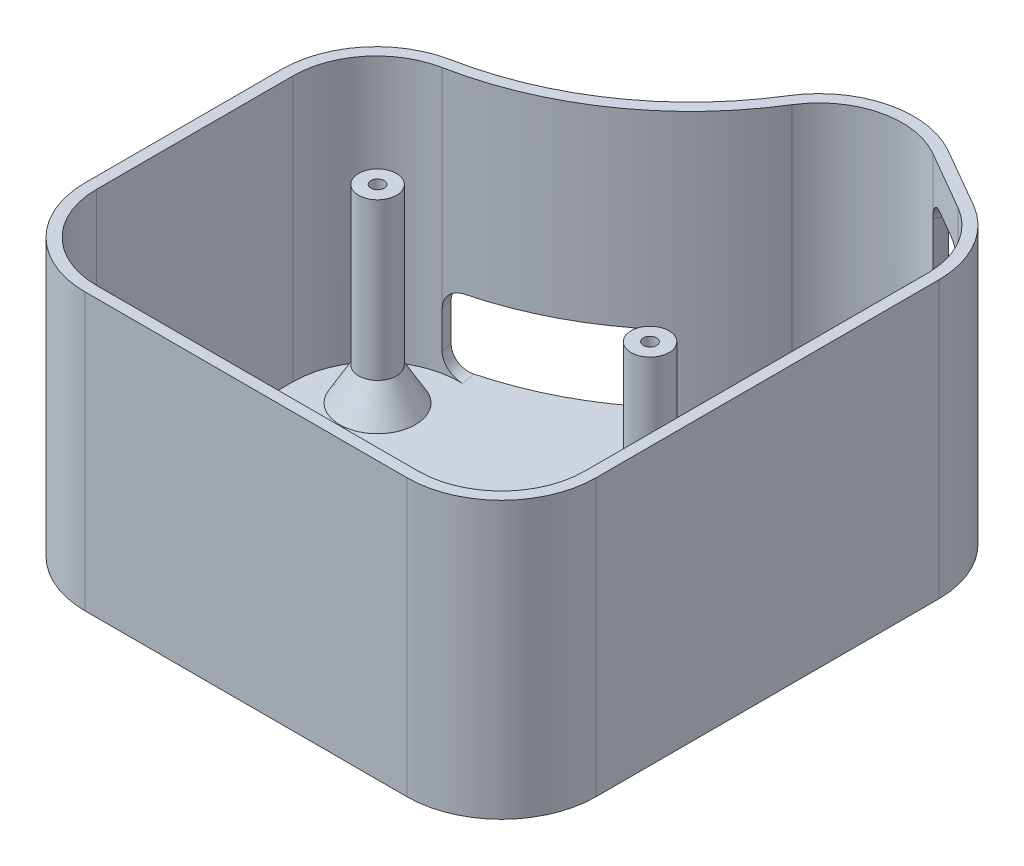
SolidWorks part; units mm, degrees
ref_plane "Front Plane" through (0, 0, 0) normal (0, 0, 1) x (1, 0, 0)
ref_plane "Top Plane" through (0, 0, 0) normal (0, 1, 0) x (1, 0, 0)
ref_plane "Right Plane" through (0, 0, 0) normal (1, 0, 0) x (0, 0, -1)
sketch "Sketch1" plane through (0, 0, 0) normal (0, 1, 0) x (1, 0, 0)
  line L1 (-130, 50) -> (130, 50)
  line L2 (-130, 50) -> (-130, -50)
  line L3 (-130, -50) -> (130, -50)
  line L4 (130, 50) -> (130, -50)
  line L5 (-130, 50) -> (130, -50) construction
  line L6 (-130, -50) -> (130, 50) construction
  point P0 (0, 0)
  dimension "D1" = 260
  dimension "D2" = 100
extrude "Boss-Extrude1" add sketch "Sketch1" along normal blind 3 contours L4 L3 L2 L1
sketch "Sketch4" plane through (0, 3, 0) normal (0, 1, 0) x (1, 0, 0)
  line L0 (-130, 50) -> (130, 50) construction
  line L1 (-77.5342, 30.2911) -> (-130, 0)
  line L2 (-130, 50) -> (-130, -50) construction
  line L3 (77.5342, 30.2911) -> (130, 0)
  line L4 (130, 50) -> (130, -50) construction
  line L5 (0, 0) -> (0, 50) construction
  line L6 (-130, -50) -> (130, -50) construction
  line L7 (-130, 0) -> (-130, 50)
  line L8 (-130, 50) -> (130, 50)
  line L9 (130, 50) -> (130, 0)
  arc A0 (-77.5342, 30.2911) -> (77.5342, 30.2911) centre (0, 50) ccw
  dimension "D1" = 160
  dimension "D2" = 60
  dimension "D3" = 60
  dimension "D4" = 50
extrude "Cut-Extrude1" cut sketch "Sketch4" against normal blind 5
sketch "Sketch5" plane through (0, 3, 0) normal (0, 1, 0) x (1, 0, 0)
  line L0 (-130, -50) -> (130, -50)
  line L1 (130, -50) -> (130, -130)
  line L2 (130, -130) -> (-130, -130)
  line L3 (-130, -130) -> (-130, -50)
  dimension "D1" = 80
extrude "Boss-Extrude4" add sketch "Sketch5" against normal blind 3
sketch "Sketch6" plane through (0, 3, 0) normal (0, 1, 0) x (1, 0, 0)
  line L6 (-79.3816, 25.7604) -> (-127, -1.7321)
  line L7 (-127, -1.7321) -> (-127, -127)
  line L8 (-127, -127) -> (127, -127)
  line L15 (127, -127) -> (127, -1.7321)
  line L16 (127, -1.7321) -> (79.3816, 25.7604)
  line L17 (-77.5342, 30.2911) -> (-130, 0)
  line L18 (-130, 0) -> (-130, -130)
  line L19 (-130, -130) -> (130, -130)
  line L20 (130, -130) -> (130, 0)
  line L27 (130, 0) -> (77.5342, 30.2911)
  line L28 (-77.5342, 30.2911) -> (-130, 0)
  line L29 (-130, 0) -> (-130, -130)
  line L30 (-130, -130) -> (130, -130)
  line L31 (130, -130) -> (130, 0)
  line L32 (130, 0) -> (77.5342, 30.2911)
  arc A3 (-79.3816, 25.7604) -> (79.3816, 25.7604) centre (0, 50) ccw
  arc A4 (-77.5342, 30.2911) -> (77.5342, 30.2911) centre (0, 50) ccw
  arc A5 (-77.5342, 30.2911) -> (77.5342, 30.2911) centre (0, 50) ccw
  dimension "D1" = 0
  dimension "D2" = 3
extrude "Boss-Extrude5" add sketch "Sketch6" along normal blind 70
sketch "Sketch7" plane through (0, 73, 0) normal (0, 1, 0) x (1, 0, 0)
  line L0 (-3.5, -32.9262) -> (-3.5, -130) construction
  line L2 (-5, -32.8493) -> (-5, -130)
  line L3 (-2, -32.9759) -> (-2, -130)
  line L4 (-2, -130) -> (-5, -130)
  line L5 (-5, 0) -> (-5, -130) construction
  line L6 (-3.5, 0) -> (-3.5, -130) construction
  line L7 (-2, 0) -> (-2, -130) construction
  line L8 (-130, -130) -> (130, -130) construction
  line L10 (-130, 0) -> (-130, -130) construction
  arc A2 (-79.3816, 25.7604) -> (79.3816, 25.7604) centre (0, 50) ccw construction
  arc A3 (-79.3816, 25.7604) -> (79.3816, 25.7604) centre (0, 50) ccw construction
  arc A4 (-5, -32.8493) -> (-2, -32.9759) centre (0, 50) ccw
  dimension "D3" = 125
  dimension "D1" = 1.5
  dimension "D2" = 1.5
extrude "Boss-Extrude6" add sketch "Sketch7" against normal up to surface (70 mm away) up to face at (0, 3, 44.1173)
sketch "Sketch9" plane through (0, 73, 0) normal (0, 1, 0) x (1, 0, 0)
  line L0 (-5, -32.8493) -> (-5, -144.8767)
  line L1 (-5, -144.8767) -> (-379.7281, -144.8767)
  line L2 (-379.7281, -144.8767) -> (-379.7281, 52.069)
  line L3 (-379.7281, 52.069) -> (-5, 52.069)
  line L4 (-5, 52.069) -> (-5, -32.8493)
extrude "Cut-Extrude3" cut sketch "Sketch9" against normal through all
sketch "Sketch10" plane through (0, 3, 0) normal (0, 1, 0) x (1, 0, 0)
  line L0 (130, -130) -> (130, 0) construction
  line L1 (14, -46.75) -> (86, -46.75) construction
  line L2 (14, -46.75) -> (14, -113.25) construction
  line L3 (14, -113.25) -> (86, -113.25) construction
  line L4 (86, -46.75) -> (86, -113.25) construction
  line L5 (14, -46.75) -> (86, -113.25) construction
  line L6 (14, -113.25) -> (86, -46.75) construction
  line L8 (-5, -130) -> (130, -130) construction
  circle A0 centre (14, -46.75) radius 5
  circle A1 centre (86, -46.75) radius 5
  circle A2 centre (86, -113.25) radius 5
  circle A3 centre (14, -113.25) radius 5
  circle A4 centre (14, -113.25) radius 1.75
  circle A5 centre (86, -113.25) radius 1.75
  circle A6 centre (14, -46.75) radius 1.75
  circle A7 centre (86, -46.75) radius 1.75
  point P0 (50, -80)
  dimension "D5" = 3.5
  dimension "D6" = 10
  dimension "D1" = 80
  dimension "D2" = 50
  dimension "D3" = 66.5
  dimension "D4" = 72
extrude "Boss-Extrude7" add sketch "Sketch10" along normal blind 50
chamfer "Chamfer1" distance 5 angle 60 4 edges at (86, 3, 108.25) (14, 3, 108.25) (86, 3, 41.75) (14, 3, 41.75) first distance on face at (14, 3, 108.25)
fillet "Fillet1" radius 22 5 edges at (127, 38, 1.7321) (127, 38, 127) (-2, 38, 127) (-2, 38, 32.9759) (79.3816, 38, -25.7604)
fillet "Fillet2" radius 25 5 edges at (130, 36.5, 0) (77.5342, 36.5, -30.2911) (-5, 36.5, 29.8436) (-5, 36.5, 130) (130, 36.5, 130)
sketch "Sketch11" plane through (0, 3, 0) normal (0, 1, 0) x (1, 0, 0)
  line L1 (52.4643, -10.3946) -> (54.4317, -12.6594)
  line L4 (130, -105) -> (130, -14.4338)
  line L5 (117.5, 7.2169) -> (101.7371, 16.3176)
  line L6 (-5, -53.0776) -> (-5, -105)
  line L7 (20, -130) -> (105, -130)
  line L14 (15.2381, -28.5353) -> (15.8095, -31.4804)
  line L16 (101.7371, 16.3176) -> (100.2371, 13.7195)
  line L17 (100.2371, 13.7195) -> (116, 4.6188)
  line L18 (116, 4.6188) -> (117.5, 7.2169)
  line L19 (117.5, 7.2169) -> (101.7371, 16.3176)
  arc A0 (15.8095, -31.4804) -> (70.5398, 6.2606) centre (0, 50) ccw construction
  arc A1 (15.8095, -31.4804) -> (54.4317, -12.6594) centre (0, 50) ccw
  arc A8 (15.2381, -28.5353) -> (67.9902, 7.8415) centre (0, 50) ccw
  arc A9 (130, -14.4338) -> (117.5, 7.2169) centre (105, -14.4338) ccw
  arc A10 (101.7371, 16.3176) -> (67.9902, 7.8415) centre (89.2371, -5.333) ccw
  arc A11 (15.2381, -28.5353) -> (-5, -53.0776) centre (20, -53.0776) ccw
  arc A14 (15.2381, -28.5353) -> (52.4643, -10.3946) centre (0, 50) ccw
  arc A18 (-5, -105) -> (20, -130) centre (20, -105) ccw
  arc A19 (105, -130) -> (130, -105) centre (105, -105) ccw
  dimension "D2" = 30
  dimension "D1" = 0
extrude "Cut-Extrude4" cut sketch "Sketch11" along normal blind 20
sketch "Sketch12" plane through (0, 3, 0) normal (0, 1, 0) x (1, 0, 0)
  line L0 (105, -105) -> (15, -105) construction
  line L1 (15, -105) -> (15, -55) construction
  circle A0 centre (89.2371, -5.333) radius 1.75
  circle A1 centre (105, -105) radius 1.75
  circle A2 centre (15, -105) radius 1.75
  circle A3 centre (15, -55) radius 1.75
  dimension "D1" = 3.5
  dimension "D3" = 50
  dimension "D2" = 90
extrude "Cut-Extrude5" cut sketch "Sketch12" against normal blind 20
sketch "Sketch14" plane through (0, 23, 0) normal (0, -1, 0) x (1, 0, 0)
  line L4 (101.7371, -16.3176) -> (117.5, -7.2169)
  line L5 (117.5, -7.2169) -> (116, -4.6188)
  line L6 (116, -4.6188) -> (100.2371, -13.7195)
  line L7 (100.2371, -13.7195) -> (101.7371, -16.3176)
  line L8 (101.7371, -16.3176) -> (117.5, -7.2169)
  line L9 (117.5, -7.2169) -> (116, -4.6188)
  line L10 (116, -4.6188) -> (100.2371, -13.7195)
  line L11 (100.2371, -13.7195) -> (101.7371, -16.3176)
  dimension "D1" = 0
extrude "Cut-Extrude6" cut sketch "Sketch14" against normal blind 40
fillet "Fillet3" radius 5 8 edges at (53.448, 3, 11.527) (53.448, 23, 11.527) (15.5238, 23, 30.0079) (15.5238, 3, 30.0079) (100.9871, 63, -15.0186) (116.75, 63, -5.9178) (116.75, 3, -5.9178) (100.9871, 3, -15.0186)
